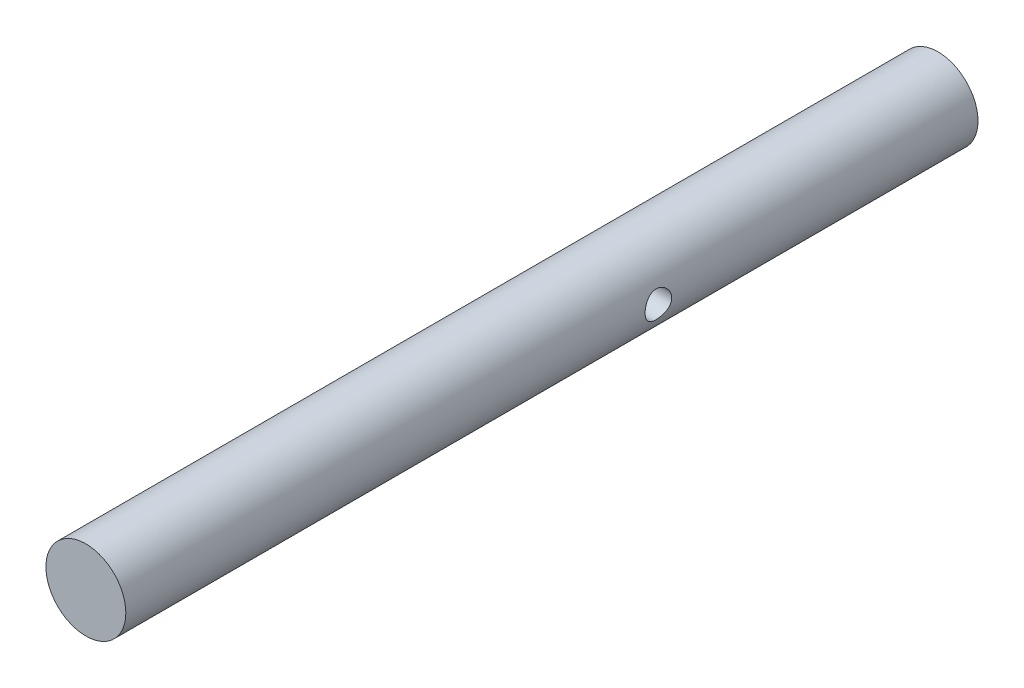
SolidWorks part; units mm, degrees
material "Nylon 101"
ref_plane "Front Plane" through (0, 0, 0) normal (0, 0, 1) x (1, 0, 0)
ref_plane "Top Plane" through (0, 0, 0) normal (0, 1, 0) x (1, 0, 0)
ref_plane "Right Plane" through (0, 0, 0) normal (1, 0, 0) x (0, 0, -1)
sketch "Sketch1" plane through (0, 0, 0) normal (0, 0, 1) x (1, 0, 0)
  circle A0 centre (0, 0) radius 4.7625
  dimension "D1" = 9.525
extrude "Boss-Extrude1" add sketch "Sketch1" along normal blind 101.6
sketch "Sketch2" plane through (0, 0, 0) normal (1, 0, 0) x (0, 0, -1)
  line L0 (0, 0) -> (-101.6, 0) construction
  line L1 (-101.6, 4.7625) -> (-101.6, -4.7625) construction
  circle A0 centre (-38.1, 0) radius 1.5875
  point P5 (0, 0)
  dimension "D2" = 3.175
  dimension "D1" = 63.5
extrude "Cut-Extrude1" cut sketch "Sketch2" against normal blind 4.7625 and the other way blind 4.7625
equation "\"LegDiam\"=0.375"
equation "\"D1@Sketch1\"=\"LegDiam\""
equation "\"LegLength\"= 4"
equation "\"D1@Boss-Extrude1\"=\"LegLength\""
equation "\"PegWhole\" =2.5"
equation "\"D1@Sketch2\"=\"PegWhole\""
equation "\"D1@Cut-Extrude1\"=\"LegDiam\"/2"
equation "\"D2@Cut-Extrude1\"=\"LegDiam\"/2"
equation "\"PegDiam\"=0.125"
equation "\"D2@Sketch2\"=\"PegDiam\""
